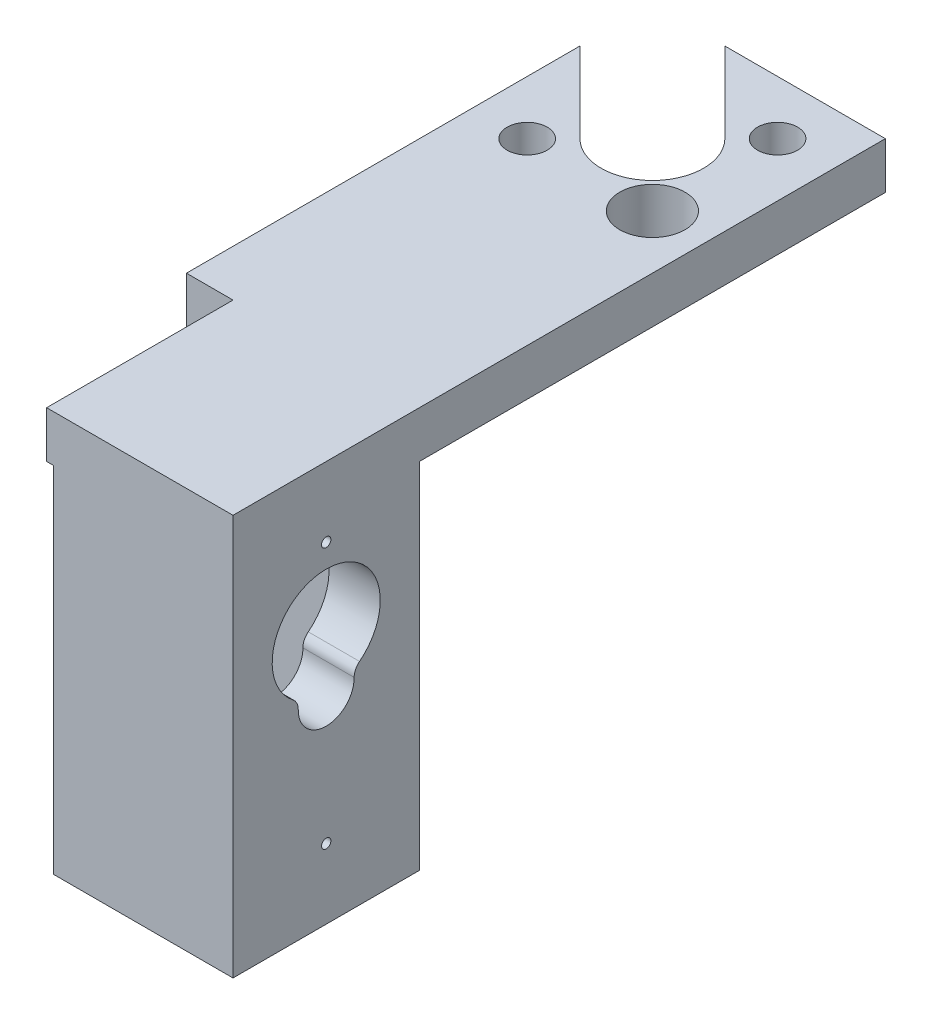
SolidWorks part; units mm, degrees
ref_plane "Front Plane" through (0, 0, 0) normal (0, 0, 1) x (1, 0, 0)
ref_plane "Top Plane" through (0, 0, 0) normal (0, 1, 0) x (1, 0, 0)
ref_plane "Right Plane" through (0, 0, 0) normal (1, 0, 0) x (0, 0, -1)
sketch "Sketch1" plane through (0, 374.6848, 0) normal (0, 1, 0) x (1, 0, 0)
  line L0 (-8.852, -261.1604) -> (-17.463, -252.5495)
  line L1 (-0.2411, -252.5495) -> (-25.2411, -252.5495)
  line L2 (-0.2411, -252.5495) -> (-0.2411, -322.5495)
  line L3 (-0.2411, -322.5495) -> (-25.2411, -322.5495)
  line L4 (-25.2411, -252.5495) -> (-25.2411, -322.5495)
  line L5 (-17.463, -252.5495) -> (-25.2411, -260.3276)
  line L6 (-25.2411, -260.3276) -> (-16.6302, -268.9385)
  circle A0 centre (-12.7411, -265.0495) radius 5.5
  circle A1 centre (-6.0236, -258.3319) radius 2.15
  circle A2 centre (-19.4586, -271.767) radius 2.15
  circle A3 centre (-6.0236, -271.767) radius 3.5
  point P13 (-12.7411, -252.5495)
  circle M6 centre (-12.7411, -265.0495) radius 12.2
  dimension "D1" = 4.3
  dimension "D2" = 11
  dimension "D6" = 7
  dimension "D3" = 12.5
  dimension "D4" = 25
  dimension "D5" = 70
extrude "Boss-Extrude1" add sketch "Sketch1" along normal blind 5 contours A3 L6 L4 L3 L2 L1 L0 M6 | A3 L0 A0 L6 A2 A1 M6 region at (-12.4582, 374.6848, 257.0662) region at (-12.4904, 374.6848, 296.9291)
sketch "Sketch2" plane through (-0.2411, 0, 0) normal (1, 0, 0) x (0, 0, -1)
  line L1 (-322.5495, 379.6848) -> (-302.5495, 379.6848)
  line L2 (-322.5495, 379.6848) -> (-322.5495, 336.6848)
  line L3 (-322.5495, 336.6848) -> (-302.5495, 336.6848)
  line L4 (-302.5495, 379.6848) -> (-302.5495, 336.6848)
  line L5 (-318.5495, 374.6848) -> (-306.5495, 374.6848)
  line L6 (-318.5495, 374.6848) -> (-318.5495, 341.6848)
  line L7 (-318.5495, 341.6848) -> (-306.5495, 341.6848)
  line L8 (-306.5495, 374.6848) -> (-306.5495, 341.6848)
  line L9 (-318.5495, 369.6848) -> (-306.5495, 369.6848)
  line L10 (-318.5495, 369.6848) -> (-318.5495, 346.6848)
  line L11 (-318.5495, 346.6848) -> (-306.5495, 346.6848)
  line L12 (-306.5495, 369.6848) -> (-306.5495, 346.6848)
  circle A0 centre (-312.5495, 363.8848) radius 5.8
  circle A1 centre (-312.5495, 358.0848) radius 3
  arc A2 (-309.5497, 358.1193) -> (-308.9743, 359.3177) centre (-308.0498, 358.1366) cw
  arc A3 (-315.5493, 358.1193) -> (-316.1246, 359.3177) centre (-317.0492, 358.1366) ccw
  point P9 (-312.5495, 336.6848)
  point P10 (-312.5495, 341.6848)
  point P21 (-318.5495, 358.1848)
  point P22 (-306.5495, 358.1848)
  point P23 (-322.5495, 358.1848)
  point P24 (-318.5495, 358.1848)
  line M15 (-322.5495, 374.6848) -> (-252.5495, 374.6848)
  dimension "D4" = 11.6
  dimension "D5" = 6
  dimension "D6" = 1.5
  dimension "D1" = 20
  dimension "D2" = 12
  dimension "D3" = 33
  dimension "D8" = 5
  dimension "D9" = 23
extrude "Boss-Extrude2" add sketch "Sketch2" against normal blind 5.5 contours L8 L7 L6 L2 L3 L4 M15 | L6 L9 L8 M15 | A1 A3 A0 L9 L6 L11 L8 A2 | L11 L6 L7 L8 region at (-0.2411, 374.2554, 320.5495) region at (-0.2411, 372.1848, 312.5495) region at (-0.2411, 354.4064, 312.5495) region at (-0.2411, 344.1848, 312.5495)
extrude "Boss-Extrude3" add sketch "Sketch2<3>" against normal blind 1.75 from surface contours L8 L7 L6 L2 L3 L4 M15 | L11 L6 L7 L8 | L6 L9 L8 M15 region at (-0.2411, 374.2554, 320.5495) region at (-0.2411, 372.1848, 312.5495) region at (-0.2411, 344.1848, 312.5495) starting at face at (-5.7411, 360.5853, 312.5495)
sketch "Sketch2<3>" plane through (-0.2411, 0, 0) normal (1, 0, 0) x (0, 0, -1) same geometry as "Sketch2"
extrude "Boss-Extrude4" add sketch "Sketch2<4>" against normal blind 12 from surface contours L8 L7 L6 L2 L3 L4 M15 region at (-0.2411, 374.2554, 320.5495) starting at face at (-7.4911, 358.1848, 312.5495)
sketch "Sketch2<4>" plane through (-0.2411, 0, 0) normal (1, 0, 0) x (0, 0, -1) same geometry as "Sketch2"
sketch "Sketch3" plane through (0, 379.6848, 0) normal (0, 1, 0) x (1, 0, 0)
  line L0 (-0.2411, -322.5495) -> (-25.2411, -322.5495) construction
  line L1 (-25.2411, -322.5495) -> (-20.2411, -322.5495)
  line L2 (-25.2411, -322.5495) -> (-25.2411, -302.5495)
  line L3 (-25.2411, -302.5495) -> (-20.2411, -302.5495)
  line L4 (-20.2411, -322.5495) -> (-20.2411, -302.5495)
  line L5 (-25.2411, -260.3276) -> (-25.2411, -322.5495) construction
  line L6 (-19.4911, -302.5495) -> (-0.2411, -302.5495) construction
  line L7 (-0.2411, -252.5495) -> (-0.2411, -322.5495) construction
  point P6 (-25.2411, -322.5495)
  dimension "D1" = 20
extrude "Cut-Extrude1" cut sketch "Sketch3" against normal through all both and the other way through all
sketch "Sketch4" plane through (-7.4911, 0, 0) normal (-1, 0, 0) x (0, 0, 1)
  line L0 (318.5495, 346.6848) -> (318.5495, 341.6848) construction
  line L1 (318.5495, 374.6848) -> (318.5495, 369.6848) construction
  line L2 (318.5495, 346.6848) -> (306.5495, 346.6848) construction
  circle A0 centre (312.5495, 372.1848) radius 0.5
  circle A1 centre (312.5495, 344.1848) radius 0.5
  point P6 (318.5495, 344.1848)
  point P9 (318.5495, 372.1848)
  point P12 (312.5495, 346.6848)
  dimension "D1" = 1
extrude "Cut-Extrude2" cut sketch "Sketch4" against normal through all both and the other way through all
